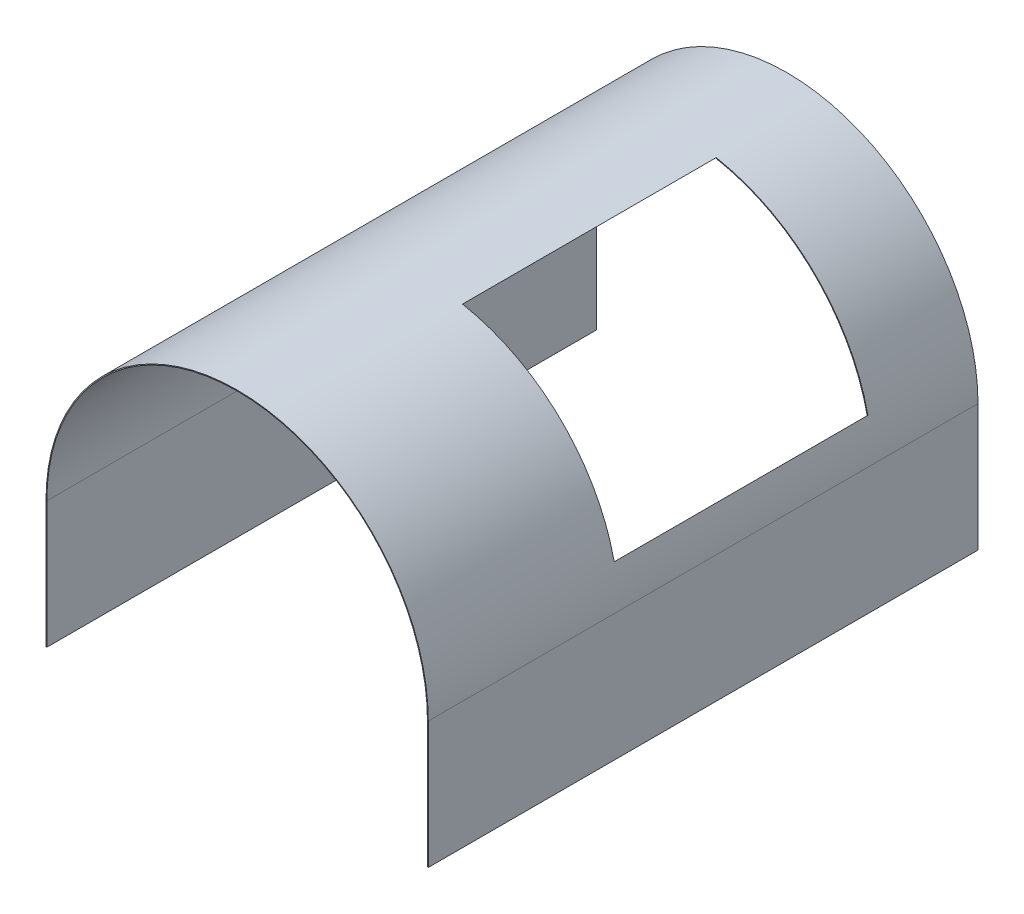
SolidWorks part; units mm, degrees
ref_plane "Front Plane" through (0, 0, 0) normal (0, 0, 1) x (1, 0, 0)
ref_plane "Top Plane" through (0, 0, 0) normal (0, 1, 0) x (1, 0, 0)
ref_plane "Right Plane" through (0, 0, 0) normal (1, 0, 0) x (0, 0, -1)
sketch "Sketch1" plane through (0, 0, 0) normal (0, 0, 1) x (1, 0, 0)
  line L0 (-228.6, -36.83) -> (-228.6, -189.23)
  line L1 (-228.6, -189.23) -> (230.632, -189.23)
  line L2 (-228.6, -189.23) -> (-228.6, 192.786) construction
  line L3 (-228.6, 192.786) -> (230.632, 192.786) construction
  line L4 (230.632, -189.23) -> (230.632, 192.786) construction
  line L5 (230.632, -36.83) -> (230.632, -189.23)
  circle A0 centre (0, 0) radius 127 construction
  arc A2 (230.632, -36.83) -> (-228.6, -36.83) centre (1.016, -36.83) ccw
  dimension "D1" = 254
  dimension "D4" = 189.23
  dimension "D5" = 228.6
  dimension "D2" = 459.232
  dimension "D3" = 382.016
extrude "Boss-Extrude1" add sketch "Sketch1" along normal blind 660.4
sketch "Sketch2" plane through (0, 0, 660.4) normal (0, 0, 1) x (1, 0, 0)
  line L0 (-228.6, -189.23) -> (230.632, -189.23) construction
  line L2 (-227.584, -36.83) -> (-227.584, -189.23)
  line L3 (-227.584, -189.23) -> (229.616, -189.23)
  line L4 (229.616, -36.83) -> (229.616, -189.23)
  line L5 (-187.6415, 88.9417) -> (229.616, -189.23) construction
  line L6 (-227.584, -189.23) -> (189.6735, 88.9417) construction
  arc A1 (229.616, -36.83) -> (-227.584, -36.83) centre (1.016, -36.83) ccw
  dimension "D2" = 457.2
extrude "Cut-Extrude1" cut sketch "Sketch2" against normal blind 660.4
ref_plane "Plane1" through (96.3898, 96.8182, 0) normal (0.7055, 0.7087, 0) x (0.7087, -0.7055, 0)
sketch "Sketch3" plane through (96.3898, 96.8182, 0) normal (0.7055, 0.7087, 0) x (0.7087, -0.7055, 0)
  line L0 (189.4276, -660.4) -> (189.4276, 0) construction
  line L1 (-102.6724, -127) -> (151.3276, -127)
  line L2 (-102.6724, -127) -> (-102.6724, -431.8)
  line L3 (-102.6724, -431.8) -> (151.3276, -431.8)
  line L4 (151.3276, -127) -> (151.3276, -431.8)
  line L5 (-102.6724, -127) -> (151.3276, -431.8) construction
  line L6 (-102.6724, -431.8) -> (151.3276, -127) construction
  line L7 (189.4276, 0) -> (-202.9111, 0) construction
  point P0 (24.3276, -279.4)
  dimension "D1" = 304.8
  dimension "D2" = 254
  dimension "D3" = 38.1
  dimension "D4" = 127
extrude "Cut-Extrude2" cut sketch "Sketch3" along normal blind 152.4
ref_plane "Plane2" through (-95.3783, 95.8022, 0) normal (0.7055, -0.7087, 0) x (-0.7087, -0.7055, 0)
sketch "Sketch4" plane through (-95.3783, 95.8022, 0) normal (0.7055, -0.7087, 0) x (-0.7087, -0.7055, 0)
  line L0 (187.9876, 0) -> (-204.3511, 0) construction
  line L1 (149.8876, -368.3) -> (73.6876, -368.3)
  line L2 (149.8876, -368.3) -> (149.8876, -190.5)
  line L3 (149.8876, -190.5) -> (73.6876, -190.5)
  line L4 (73.6876, -368.3) -> (73.6876, -190.5)
  line L5 (149.8876, -368.3) -> (73.6876, -190.5) construction
  line L6 (149.8876, -190.5) -> (73.6876, -368.3) construction
  line L7 (187.9876, -660.4) -> (187.9876, 0) construction
  point P0 (111.7876, -279.4)
  dimension "D1" = 177.8
  dimension "D2" = 76.2
  dimension "D3" = 190.5
  dimension "D4" = 38.1
extrude "Cut-Extrude3" cut sketch "Sketch4" against normal blind 152.4
